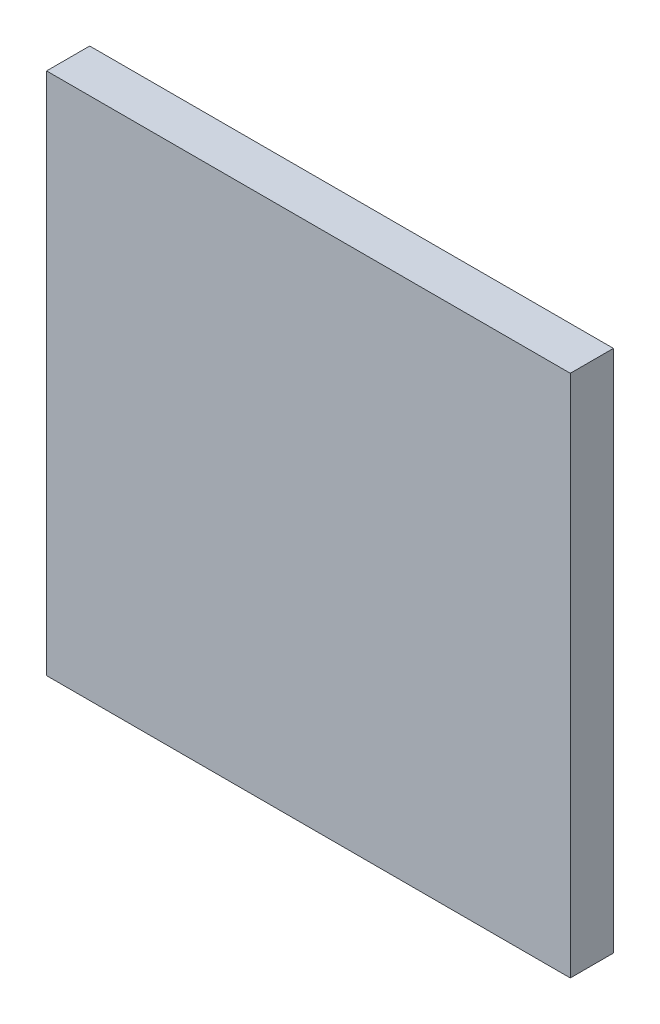
SolidWorks part; units mm, degrees
note: The reader was unsure of these and kept them because the rebuilt part matched: thickness of "Базовая кромка1", "Листовой металл1".
material "Простая углеродистая сталь"
ref_plane "Спереди" through (0, 0, 0) normal (0, 0, 1) x (1, 0, 0)
ref_plane "Сверху" through (0, 0, 0) normal (0, 1, 0) x (1, 0, 0)
ref_plane "Справа" through (0, 0, 0) normal (1, 0, 0) x (0, 0, -1)
sketch "Эскиз1" plane through (0, 0, 0) normal (0, 0, 1) x (1, 0, 0)
  line L0 (85, 0) -> (85, -170) construction
  line L1 (0, 0) -> (170, 0)
  line L2 (0, 0) -> (0, -170)
  line L3 (0, -170) -> (170, -170)
  line L4 (170, 0) -> (170, -170)
  line L5 (0, -85) -> (170, -85) construction
  dimension "D1" = 170
  dimension "D2" = 170
base flange "Базовая кромка1" sketch "Эскиз1" thickness 14 reverse thickness direction no parameters "D1"=3
sketch "Сгиб-Линии1" [suppressed] plane through (0, 0, 0) normal (0, 1, 0) x (1, 0, 0)
sketch "Граничная рамка1" [suppressed] plane through (0, 0, 0) normal (0, 1, 0) x (1, 0, 0)
sheet metal parameters "Листовой металл1" thickness 14 parameters "D1"=3, "D7"=10
flat pattern "Развертка1" [suppressed]
sketch "Сгиб-Линии2" plane through (0, 0, 0) normal (0, 1, 0) x (1, 0, 0)
sketch3d "Граничная рамка2" [suppressed]
  line L0 (0, -170, 0) -> (170, -170, 0) construction
  line L1 (0, 0, 0) -> (170, 0, 0) construction
  line L2 (0, -170, 0) -> (0, 0, 0) construction
  line L3 (170, -170, 0) -> (170, 0, 0) construction
